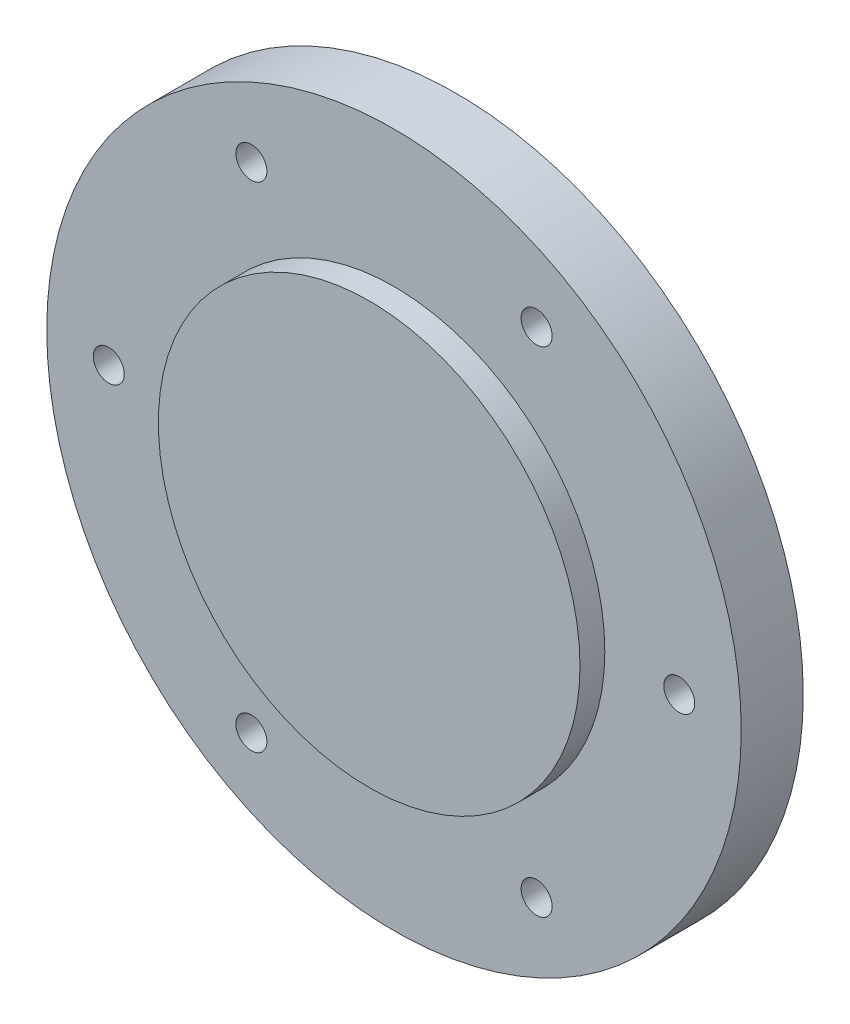
SolidWorks part; units mm, degrees
ref_plane "Front Plane" through (0, 0, 0) normal (0, 0, 1) x (1, 0, 0)
ref_plane "Top Plane" through (0, 0, 0) normal (0, 1, 0) x (1, 0, 0)
ref_plane "Right Plane" through (0, 0, 0) normal (1, 0, 0) x (0, 0, -1)
sketch "SK_Disc" plane through (0, 0, 0) normal (0, 0, 1) x (1, 0, 0)
  circle A0 centre (0, 0) radius 28
  dimension "D_disc" = 56
extrude "Output_Disc" add sketch "SK_Disc" along normal blind 5
ref_plane "PL_Mount" through (0, 0, 5) normal (0, 0, 1) x (1, 0, 0)
sketch "SK_Pilot" plane through (0, 0, 5) normal (0, 0, 1) x (1, 0, 0)
  circle A0 centre (0, 0) radius 17
  dimension "D_pil" = 34
extrude "Pilot_Boss" add sketch "SK_Pilot" along normal blind 2
sketch "SK_OutHole" plane through (0, 0, 5) normal (0, 0, 1) x (1, 0, 0)
  circle A0 centre (23, 0) radius 1.25
  dimension "D_oh" = 2.5
  dimension "R_oh" = 23
extrude "Output_Tapped_Hole" cut sketch "SK_OutHole" against normal blind 5
ref_axis "AX_Joint" through (0, 0, -0.35) along (0, 0, 1)
pattern_circular "Output_Hole_Pattern" count 6 over 360 about axis through (0, 0, -0.35) along (0, 0, 1) of "Output_Tapped_Hole"
equation "\"D_out\" = 56"
equation "\"T_out\" = 5"
equation "\"PCD_out\" = 46"
equation "\"D_pilot\" = 34"
equation "\"H_pilot\" = 2"
equation "\"D_out_hole\" = 2.5"
equation "\"D_disc@SK_Disc\" = \"D_out\""
equation "\"D1@Output_Disc\" = \"T_out\""
equation "\"D_pil@SK_Pilot\" = \"D_pilot\""
equation "\"D1@Pilot_Boss\" = \"H_pilot\""
equation "\"D_oh@SK_OutHole\" = \"D_out_hole\""
equation "\"R_oh@SK_OutHole\" = \"PCD_out\"/2"
